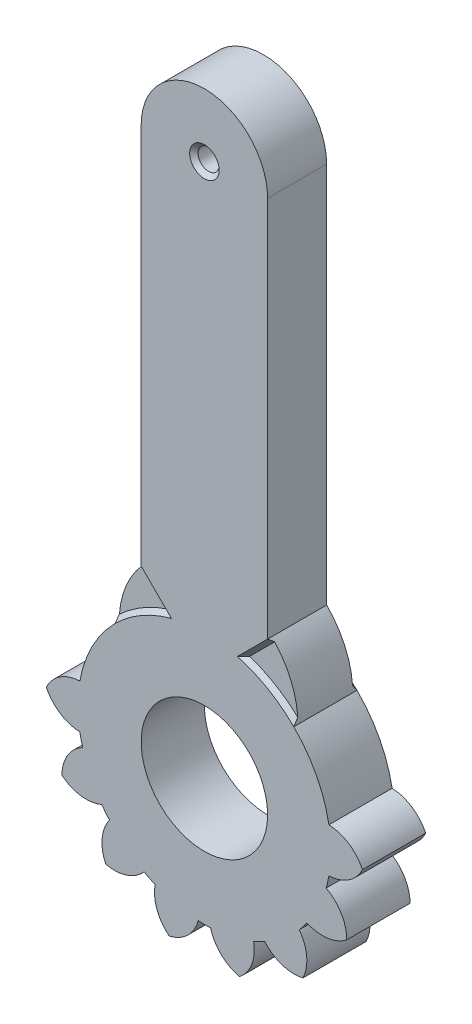
SolidWorks part; units mm, degrees
ref_plane "Front Plane" through (0, 0, 0) normal (0, 0, 1) x (1, 0, 0)
ref_plane "Top Plane" through (0, 0, 0) normal (0, 1, 0) x (1, 0, 0)
ref_plane "Right Plane" through (0, 0, 0) normal (1, 0, 0) x (0, 0, -1)
sketch "Sketch2" plane through (0, 0, 0) normal (0, 0, 1) x (1, 0, 0)
  circle A0 centre (0, 0) radius 15
  circle A1 centre (0, 0) radius 30
  dimension "D1" = 30
  dimension "D2" = 60
extrude "Boss-Extrude1" add sketch "Sketch2" along normal mid plane 15
sketch "Sketch4" plane through (0, 0, 0) normal (0, 0, 1) x (1, 0, 0)
  line L1 (0, 0) -> (0, 35.9696) construction
  circle A0 centre (0, 0) radius 30 construction
  arc A1 (-21.2132, 21.2132) -> (21.2132, 21.2132) centre (0, 21.1305) cw
  arc A2 (-21.2132, 21.2132) -> (21.2132, 21.2132) centre (0, 0) cw
extrude "Boss-Extrude2" add sketch "Sketch4" along normal mid plane 13
chamfer "Chamfer2" distance 1 angle 45 2 edges at (0, 30, 6.5) (0, 30, -6.5)
sketch "Sketch5" plane through (0, 0, -6.5) normal (0, 0, -1) x (-1, 0, 0)
  line L0 (0, 42.3438) -> (0, -1.647) construction
  line L1 (0, 21.1305) -> (-15.0001, 36.1306)
  line L2 (0, 21.1305) -> (15.0001, 36.1306)
  line L3 (-15.0001, 36.1306) -> (-15.0001, 126.7165)
  line L4 (15.0001, 36.1306) -> (15.0001, 126.7165)
  arc A0 (-15.0001, 126.7165) -> (15.0001, 126.7165) centre (0, 126.7165) cw
  arc A1 (21.1584, 22.6566) -> (-21.1584, 22.6566) centre (0, 21.1305) ccw construction
  dimension "D1" = 45
extrude "Boss-Extrude3" add sketch "Sketch5" against normal blind 14
chamfer "Chamfer3" distance 1 angle 45 2 edges at (11.8205, 32.951, 6.5) (-11.8205, 32.951, 6.5)
sketch "Sketch6" plane through (0, 0, 7.5) normal (0, 0, 1) x (1, 0, 0)
  circle A0 centre (0, 126.7165) radius 2.5
  dimension "D1" = 5
extrude "Cut-Extrude1" cut sketch "Sketch6" against normal blind 14
chamfer "Chamfer4" distance 1 angle 45 1 edges at (2.5, 126.7165, 7.5)
chamfer "Chamfer5" distance 1 angle 45 1 edges at (2.5, 126.7165, -6.5)
sketch "Sketch7" plane through (0, 0, 7.5) normal (0, 0, 1) x (1, 0, 0)
  line L0 (0, 0) -> (-8.1312, 0) construction
  line L1 (0, 0) -> (0, 3.2839) construction
  circle A0 centre (0, 0) radius 30
  circle A1 centre (0, 0) radius 37.5
  arc A2 (-29.5389, -5.2394) -> (-37.5, 0) centre (-29.1857, 3.9652) cw
  arc A3 (-29.5389, 5.2394) -> (-37.5, 0) centre (-29.1857, -3.9652) ccw
  arc A4 (-28.887, -8.0959) -> (-33.7863, -16.2706) centre (-24.575, -16.2357) ccw
  arc A5 (-24.3403, -17.537) -> (-33.7863, -16.2706) centre (-28.0159, -9.0907) cw
  arc A6 (-22.5136, -19.8277) -> (-23.3809, -29.3187) centre (-15.0969, -25.2906) ccw
  arc A7 (-14.3209, -26.3612) -> (-23.3809, -29.3187) centre (-21.2971, -20.346) cw
  arc A8 (-11.6811, -27.6324) -> (-8.3445, -36.5598) centre (-2.6286, -29.3363) ccw
  arc A9 (-1.465, -29.9642) -> (-8.3445, -36.5598) centre (-10.3602, -27.5716) cw
  arc A10 (1.465, -29.9642) -> (8.3445, -36.5598) centre (10.3602, -27.5716) ccw
  arc A11 (11.6811, -27.6324) -> (8.3445, -36.5598) centre (2.6286, -29.3363) cw
  arc A12 (14.3209, -26.3612) -> (23.3809, -29.3187) centre (21.2971, -20.346) ccw
  arc A13 (22.5136, -19.8277) -> (23.3809, -29.3187) centre (15.0969, -25.2906) cw
  arc A14 (24.3403, -17.537) -> (33.7863, -16.2706) centre (28.0159, -9.0907) ccw
  arc A15 (28.887, -8.0959) -> (33.7863, -16.2706) centre (24.575, -16.2357) cw
  arc A16 (29.5389, -5.2394) -> (37.5, 0) centre (29.1857, 3.9652) ccw
  arc A17 (29.5389, 5.2394) -> (37.5, 0) centre (29.1857, -3.9652) cw
  point P51 (0, 0)
  arc M10 (-21.2132, 21.2132) -> (21.2132, 21.2132) centre (0, 0) ccw
  dimension "D1" = 75
  dimension "D2" = 8
extrude "Boss-Extrude4" add sketch "Sketch7" against normal blind 15 contours A0 A3 A2 | A5 A4 M10 | A7 A6 M10 | A9 A8 M10 | A11 A10 M10 | A13 A12 M10 | A15 A14 M10 | A17 A16 M10 region at (32.8352, 0, 7.5) region at (29.5835, -14.2467, 7.5) region at (-32.8352, 0, 7.5) region at (-29.5835, -14.2467, 7.5) region at (20.4724, -25.6716, 7.5) region at (-20.4724, -25.6716, 7.5) region at (7.3065, -32.012, 7.5) region at (-7.3065, -32.012, 7.5)
